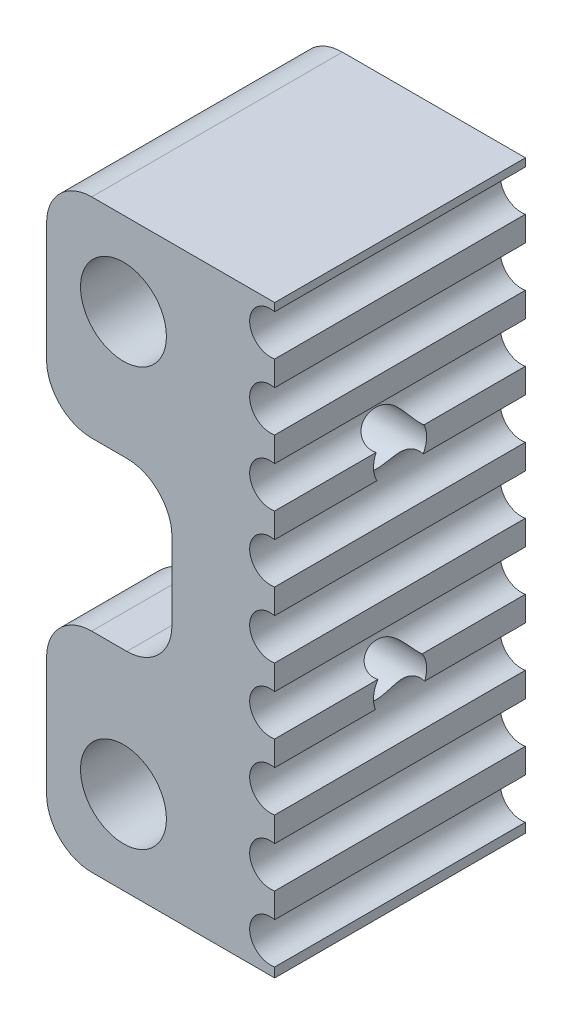
SolidWorks part; units mm, degrees
material "6061-T6 (SS)"
ref_plane "Front Plane" through (0, 0, 0) normal (0, 0, 1) x (1, 0, 0)
ref_plane "Top Plane" through (0, 0, 0) normal (0, 1, 0) x (1, 0, 0)
ref_plane "Right Plane" through (0, 0, 0) normal (1, 0, 0) x (0, 0, -1)
sketch "Sketch1" plane through (0, 0, 0) normal (0, 0, 1) x (1, 0, 0)
  line L0 (0, 0) -> (17.3355, 0)
  line L1 (17.3355, 0) -> (17.3355, 44.45)
  line L2 (17.3355, 44.45) -> (0, 44.45)
  line L3 (0, 44.45) -> (0, 28.575)
  line L4 (0, 28.575) -> (9.525, 28.575)
  line L5 (9.525, 28.575) -> (9.525, 15.875)
  line L6 (9.525, 15.875) -> (0, 15.875)
  line L7 (0, 15.875) -> (0, 0)
  dimension "D1" = 44.45
  dimension "D2" = 12.7
  dimension "D3" = 15.875
  dimension "D4" = 9.525
  dimension "D5" = 17.3355
extrude "Boss-Extrude1" add sketch "Sketch1" along normal blind 19.05
hole_wizard "1/4 Clearance Hole1" positions "Sketch2" profile "Sketch3" hole size "1/4" standard "ANSI Inch" end condition through all
sketch "Sketch2" plane through (0, 0, 19.05) normal (0, 0, 1) x (1, 0, 0)
  line L0 (17.3355, 44.45) -> (0, 44.45) construction
  line L1 (0, 44.45) -> (0, 28.575) construction
  line L2 (9.525, 22.225) -> (17.3355, 22.225) construction
  line L3 (9.525, 28.575) -> (9.525, 15.875) construction
  line L4 (17.3355, 0) -> (17.3355, 44.45) construction
  point P0 (5.842, 38.1)
  point P21 (5.842, 6.35)
  dimension "D1" = 6.35
  dimension "D2" = 5.842
sketch "Sketch3" plane through (5.842, 38.1, 19.05) normal (1, 0, 0) x (0, -1, 0)
  line L0 (0, 0) -> (0, 19.05)
  line L1 (0, 19.05) -> (3.2639, 19.05)
  line L2 (3.2639, 19.05) -> (3.2639, 0)
  line L5 (3.2639, 0) -> (0, 0)
  line L11 (0, -6.35) -> (0, 107.95) construction
  dimension "Thru Hole Dia." = 6.5278
  dimension "Thru Hole Depth" = 19.05
hole_wizard "#10-32 Tapped Hole1" positions "Sketch4" profile "Sketch5" tap size "#10-32" standard "ANSI Inch" end condition through all
sketch "Sketch4" plane through (17.3355, 0, 0) normal (1, 0, 0) x (0, 0, -1)
  line L3 (-9.525, 44.45) -> (-9.525, 29.845) construction
  line L4 (-19.05, 44.45) -> (0, 44.45) construction
  line L6 (-9.525, 0) -> (-9.525, 14.605) construction
  line L7 (-19.05, 0) -> (0, 0) construction
  point P11 (-9.525, 29.845)
  point P17 (-9.525, 14.605)
  dimension "D1" = 14.605
sketch "Sketch5" plane through (17.3355, 14.605, 9.525) normal (0, 1, 0) x (0, 0, -1)
  line L0 (0, 0) -> (0, 17.3355)
  line L1 (0, 17.3355) -> (2.0193, 17.3355)
  line L2 (2.0193, 17.3355) -> (2.0193, 0)
  line L5 (2.0193, 0) -> (0, 0)
  line L11 (0, -6.35) -> (0, 107.95) construction
  dimension "Thru Tap Drill Dia." = 4.0386
  dimension "Thru Tap Drill Depth" = 17.3355
cosmetic thread "Hole Thread1" parameters "D2"=4.826
cosmetic thread "Hole Thread2" parameters "D2"=4.826
sketch "Sketch6" plane through (0, 0, 19.05) normal (0, 0, 1) x (1, 0, 0)
  line L0 (17.3355, 0) -> (17.3355, 44.45) construction
  line L1 (0, 0) -> (17.3355, 0) construction
  circle A0 centre (17.018, 2.2809) radius 1.5875
  point P2 (16.814, 1.855)
  dimension "D1" = 3.175
  dimension "D2" = 0.3175
  dimension "D3" = 2.2809
extrude "Cut-Extrude1" cut sketch "Sketch6" against normal through all and the other way through all
pattern_linear "LPattern1" count 9 spacing 5.0013 along (0, 1, 0) of "Cut-Extrude1"
fillet "Fillet1" radius 3.429 6 edges at (0, 0, 9.525) (9.525, 15.875, 15.0725) (0, 15.875, 3.9775) (9.525, 28.575, 3.9775) (0, 28.575, 3.9775) (0, 44.45, 9.525)
